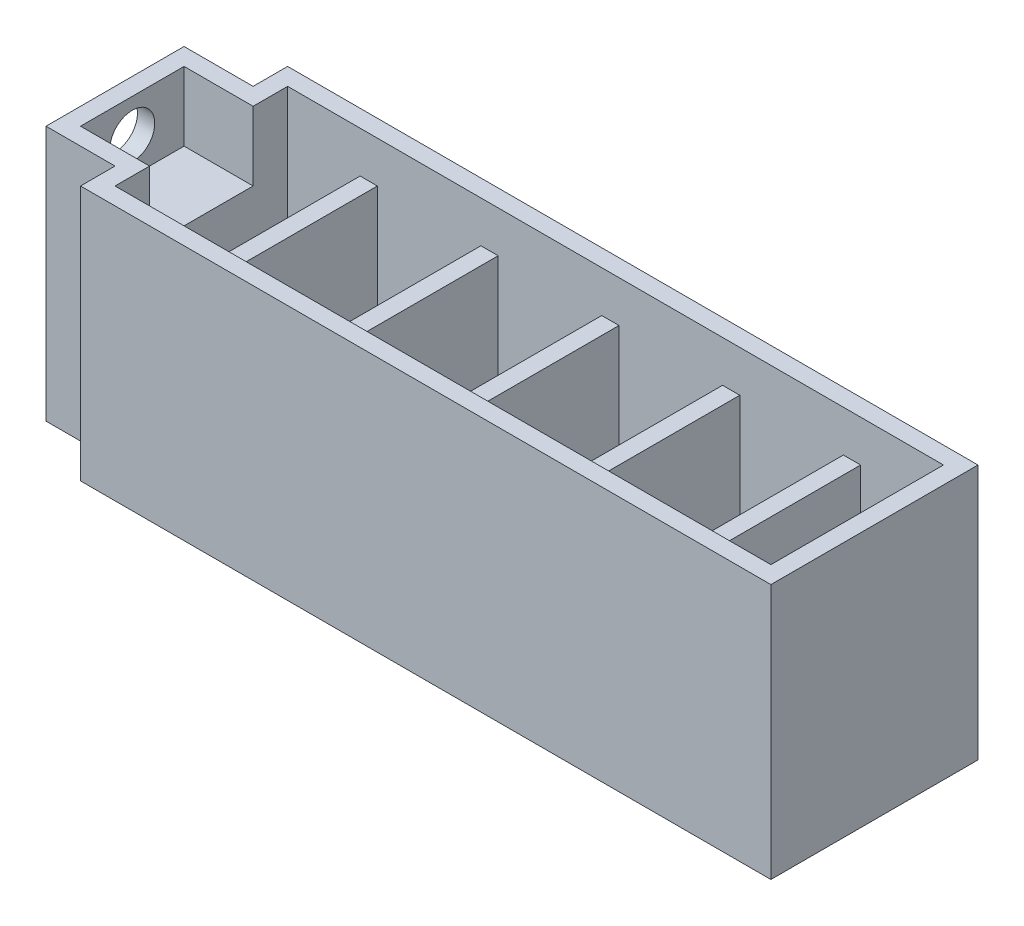
SolidWorks part; units mm, degrees
ref_plane "前视基准面" through (0, 0, 0) normal (0, 0, 1) x (1, 0, 0)
ref_plane "上视基准面" through (0, 0, 0) normal (0, 1, 0) x (1, 0, 0)
ref_plane "右视基准面" through (0, 0, 0) normal (1, 0, 0) x (0, 0, -1)
sketch "草图2" plane through (0, 0, 0) normal (0, 1, 0) x (1, 0, 0)
  line L0 (10, 15) -> (10, 10)
  line L1 (10, 15) -> (110, 15)
  line L3 (10, -15) -> (110, -15)
  line L4 (110, 15) -> (110, -15)
  line L5 (10, -10) -> (0, -10)
  line L7 (10, 10) -> (0, 10)
  line L8 (0, -10) -> (0, 10)
  line L9 (10, -10) -> (10, -15)
  line L10 (12.5, 12.5) -> (107.5, 12.5)
  line L11 (107.5, 12.5) -> (107.5, -12.5)
  line L12 (12.5, -12.5) -> (107.5, -12.5)
  line L13 (12.5, -7.5) -> (12.5, -12.5)
  line L14 (12.5, -7.5) -> (2.5, -7.5)
  line L15 (2.5, -7.5) -> (2.5, 7.5)
  line L16 (12.5, 7.5) -> (2.5, 7.5)
  line L17 (12.5, 12.5) -> (12.5, 7.5)
  point P4 (0.4438, 14.9567)
  dimension "D1" = 30
  dimension "D2" = 10
  dimension "100" = 100
  dimension "D3" = 5
  dimension "D4" = 5
  dimension "D5" = 2.5
extrude "凸台-拉伸2" add sketch "草图2" along normal blind 1 contours L4 L1 L3 | L10 L11 L12 L13 L14 L15 L16 L17 region at (60, 0, -13.8598)
extrude "凸台-拉伸3" add sketch "草图2<3>" along normal blind 37
sketch "草图2<3>" plane through (0, 0, 0) normal (0, 1, 0) x (1, 0, 0) same geometry as "草图2"
sketch "草图3" plane through (0, 1, 0) normal (0, 1, 0) x (1, 0, 0)
  line L0 (107.5, 12.5) -> (12.5, 12.5) construction
  line L1 (23, 12.5) -> (25.5, 12.5)
  line L2 (23, 12.5) -> (23, -12.5)
  line L3 (23, -12.5) -> (25.5, -12.5)
  line L4 (25.5, 12.5) -> (25.5, -12.5)
  line L5 (12.5, -12.5) -> (107.5, -12.5) construction
  line L6 (12.5, 12.5) -> (107.5, 12.5) construction
  line L7 (40.5, 12.5) -> (43, 12.5)
  line L8 (40.5, 12.5) -> (40.5, -12.5)
  line L9 (40.5, -12.5) -> (43, -12.5)
  line L10 (43, 12.5) -> (43, -12.5)
  line L11 (107.5, -12.5) -> (12.5, -12.5) construction
  line L12 (58, 12.5) -> (60.5, 12.5)
  line L13 (58, 12.5) -> (58, -12.5)
  line L14 (58, -12.5) -> (60.5, -12.5)
  line L15 (60.5, 12.5) -> (60.5, -12.5)
  line L16 (75.5, 12.5) -> (78, 12.5)
  line L17 (75.5, 12.5) -> (75.5, -12.5)
  line L18 (75.5, -12.5) -> (78, -12.5)
  line L19 (78, 12.5) -> (78, -12.5)
  line L20 (107.5, 12.5) -> (107.5, -12.5) construction
  line L21 (93, 12.5) -> (95.5, 12.5)
  line L22 (93, 12.5) -> (93, -12.5)
  line L23 (93, -12.5) -> (95.5, -12.5)
  line L24 (95.5, 12.5) -> (95.5, -12.5)
  dimension "D1" = 2.5
  dimension "D2" = 15
  dimension "D3" = 15
  dimension "D4" = 15
  dimension "D5" = 15
  dimension "D6" = 12
extrude "凸台-拉伸4" add sketch "草图3" along normal blind 30
sketch "草图4" plane through (0, 1, 0) normal (0, 1, 0) x (1, 0, 0)
  line L0 (12.5, 7.5) -> (12.5, -7.5)
  line L1 (12.5, -7.5) -> (2.5, -7.5) construction
  line L2 (2.5, -7.5) -> (2.5, 7.5) construction
  line L3 (2.5, 7.5) -> (12.5, 7.5) construction
  line L4 (12.5, -7.5) -> (2.5, -7.5)
  line L5 (2.5, -7.5) -> (2.5, 7.5)
  line L6 (2.5, 7.5) -> (12.5, 7.5)
extrude "凸台-拉伸5" add sketch "草图4" along normal blind 26
sketch "草图5" plane through (0, 0, 0) normal (-1, 0, 0) x (0, 0, 1)
  line L0 (-10, 37) -> (10, 37) construction
  circle A0 centre (0, 32) radius 3.25
  dimension "D1" = 6.5
  dimension "D2" = 5
extrude "切除-拉伸1" cut sketch "草图5" against normal up to next
